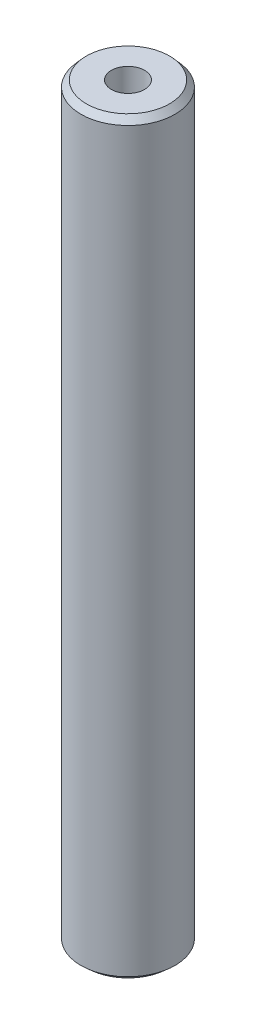
SolidWorks part; units mm, degrees
ref_plane "Front Plane" through (0, 0, 0) normal (0, 0, 1) x (1, 0, 0)
ref_plane "Top Plane" through (0, 0, 0) normal (0, 1, 0) x (1, 0, 0)
ref_plane "Right Plane" through (0, 0, 0) normal (1, 0, 0) x (0, 0, -1)
sketch "Sketch1" plane through (0, 0, 0) normal (0, 1, 0) x (1, 0, 0)
  circle A0 centre (0, 0) radius 25
  dimension "SHAFT_OD" = 50
extrude "Boss-Extrude1" add sketch "Sketch1" along normal blind 397.9956
sketch "Sketch2" plane through (0, 0, 0) normal (0, 1, 0) x (1, 0, 0)
  circle A0 centre (0, 0) radius 8.8269
  dimension "BORE_D" = 17.6538
extrude "Cut-Extrude1" cut sketch "Sketch2" along normal through all
chamfer "Chamfer1" distance 3.3261 angle 41.422 2 edges at (0, 397.9956, 25) (0, 0, 25) first distance on face at (0, 397.9956, 25) first distance on face at (0, 0, 8.8269)
